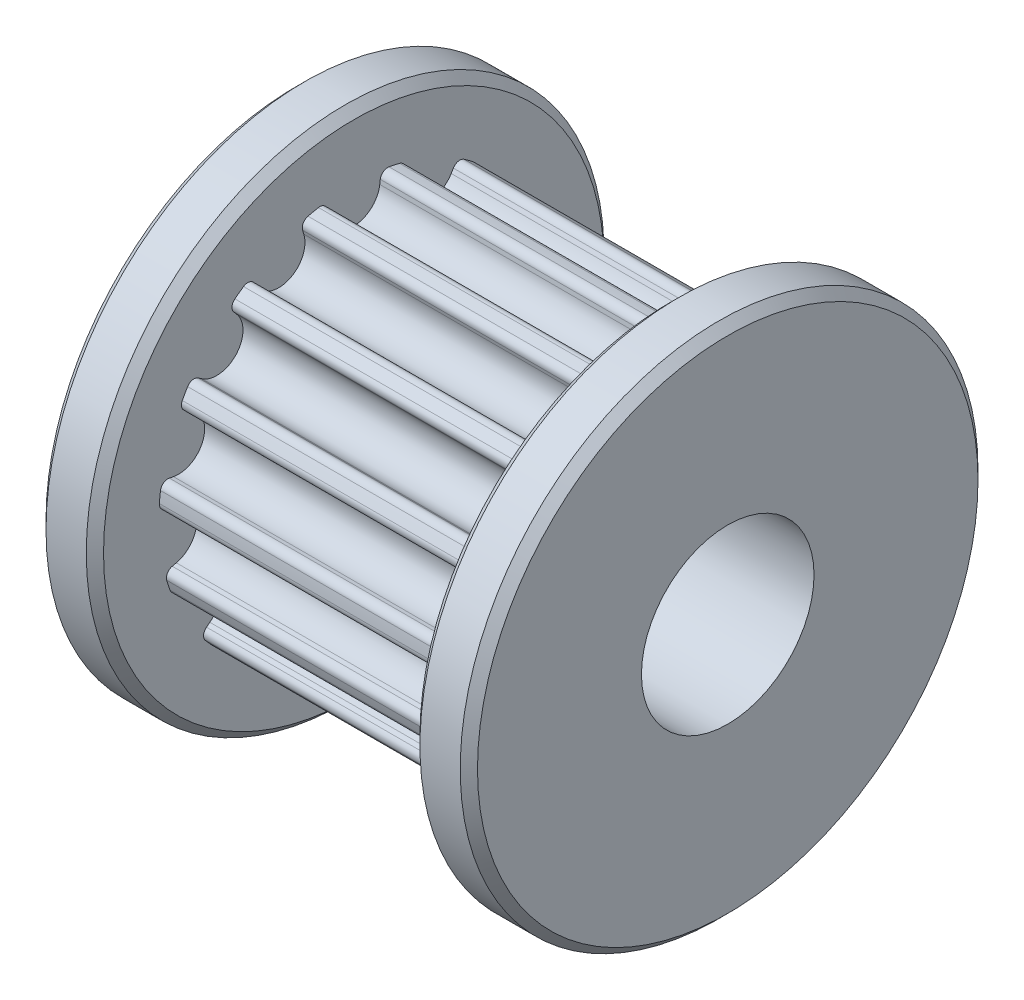
SolidWorks part; units mm, degrees
ref_plane "前视基准面" through (0, 0, 0) normal (0, 0, 1) x (1, 0, 0)
ref_plane "上视基准面" through (0, 0, 0) normal (0, 1, 0) x (1, 0, 0)
ref_plane "右视基准面" through (0, 0, 0) normal (1, 0, 0) x (0, 0, -1)
sketch "草图1" plane through (0, 0, 0) normal (0, 0, 1) x (1, 0, 0)
  line L0 (0, 0) -> (64.8368, 0) construction
  line L1 (0, 1.3558) -> (0, 6.779)
  line L2 (0, 6.779) -> (11, 6.779)
  line L3 (11, 6.779) -> (11, 2.7116)
  line L4 (11, 2.7116) -> (20, 2.7116)
  line L5 (20, 2.7116) -> (20, 1.3558)
  line L6 (20, 1.3558) -> (0, 1.3558)
  dimension "L" = 20
  dimension "B" = 11
  dimension "d" = 2.7116
  dimension "d1" = 5.4232
  dimension "da" = 13.558
revolve "旋转1" add sketch "草图1" angle 360 about L0
chamfer "倒角1" distance 1 angle 45 2 edges at (20, 0, 1.3558) (0, 0, 1.3558)
sketch "草图4" plane through (0, 0, 0) normal (-1, 0, 0) x (0, 0, 1)
  line L1 (-1, 0.9155) -> (1, 0.9155)
  line L2 (-1, 0.9155) -> (-1, 2.3558)
  line L3 (-1, 2.3558) -> (1, 2.3558)
  line L4 (1, 0.9155) -> (1, 2.3558)
  circle A0 centre (0, 0) radius 1.3558 construction
  point P6 (0, 2.3558)
  dimension "键槽高度" = 2.3558
  dimension "键槽宽度" = 2
  dimension "t1" = 1
extrude "切除-拉伸1" cut sketch "草图4" against normal through all
sketch "草图6" plane through (0, 0, 0) normal (1, 0, 0) x (0, 0, -1)
  line L0 (0, 0) -> (0, 30.6512) construction
  line L1 (0.921, 6.4432) -> (0.9032, 6.2981)
  line L2 (1.4809, 6.6153) -> (1.6775, 8.2168)
  line L3 (-1.4809, 6.6153) -> (-1.6775, 8.2168)
  line L4 (-0.921, 6.4432) -> (-0.9032, 6.2981)
  circle A0 centre (0, 0) radius 6.779 construction
  circle A1 centre (0, 0) radius 5.499 construction
  arc A2 (-0.9032, 6.2981) -> (0.9032, 6.2981) centre (0, 6.409) ccw
  arc A3 (1.6775, 8.2168) -> (-1.6775, 8.2168) centre (0, 0) ccw
  arc A4 (0.921, 6.4432) -> (1.2261, 6.6672) centre (1.1791, 6.4115) cw
  arc A5 (1.2261, 6.6672) -> (1.4809, 6.6153) centre (0, 0) cw
  arc A6 (-1.2261, 6.6672) -> (-1.4809, 6.6153) centre (0, 0) ccw
  arc A7 (-0.921, 6.4432) -> (-1.2261, 6.6672) centre (-1.1791, 6.4115) ccw
  point P7 (0, 1.9)
  point P8 (0, 29.3712)
  point P15 (0.954, 6.7115)
  dimension "D1" = 10.998
  dimension "ra" = 0.26
  dimension "rf" = 0.91
  dimension "hg" = 1.28
  dimension "D3" = 0.26
  dimension "D4" = 1.6136
  dimension "angle" = 14
  dimension "bw" = 1.9
extrude "切除-拉伸2" cut sketch "草图6" along normal up to next
ref_axis "基准轴1" through (-1.4, 0, 0) along (1, 0, 0)
pattern_circular "阵列(圆周)3" count 15 over 360 about axis through (-1.4, 0, 0) along (1, 0, 0) of "切除-拉伸2"
sketch "草图7" plane through (0, 0, 0) normal (-1, 0, 0) x (0, 0, 1)
  circle A0 centre (0, 0) radius 3
  dimension "D1" = 6
extrude "切除-拉伸3" cut sketch "草图7" against normal through all
sketch "草图9" plane through (0, 0, 0) normal (-1, 0, 0) x (0, 0, 1)
  circle A0 centre (0, 0) radius 9
  circle A1 centre (0, 0) radius 3 construction
  circle A2 centre (0, 0) radius 3
  dimension "D1" = 18
extrude "凸台-拉伸1" add sketch "草图9" along normal blind 2
sketch "草图10" plane through (11, 0, 0) normal (1, 0, 0) x (0, 0, -1)
  circle A0 centre (0, 0) radius 9
  circle A1 centre (0, 0) radius 9 construction
  circle A2 centre (0, 0) radius 3 construction
  circle A3 centre (0, 0) radius 3
extrude "凸台-拉伸2" add sketch "草图10" along normal blind 2
chamfer "倒角2" distance 0.3 angle 45 4 edges at (13, 0, -9) (11, 0, -9) (0, 0, 9) (-2, 0, 9)
equation "\"键槽高度@草图4\" = \"d@草图1\" / 2  + \"t1@草图4\""
equation "\"D1@草图6\" = \"da@草图1\"  - \"hg@草图6\" - \"hg@草图6\""
equation "\"D3@草图6\" = \"ra@草图6\""
